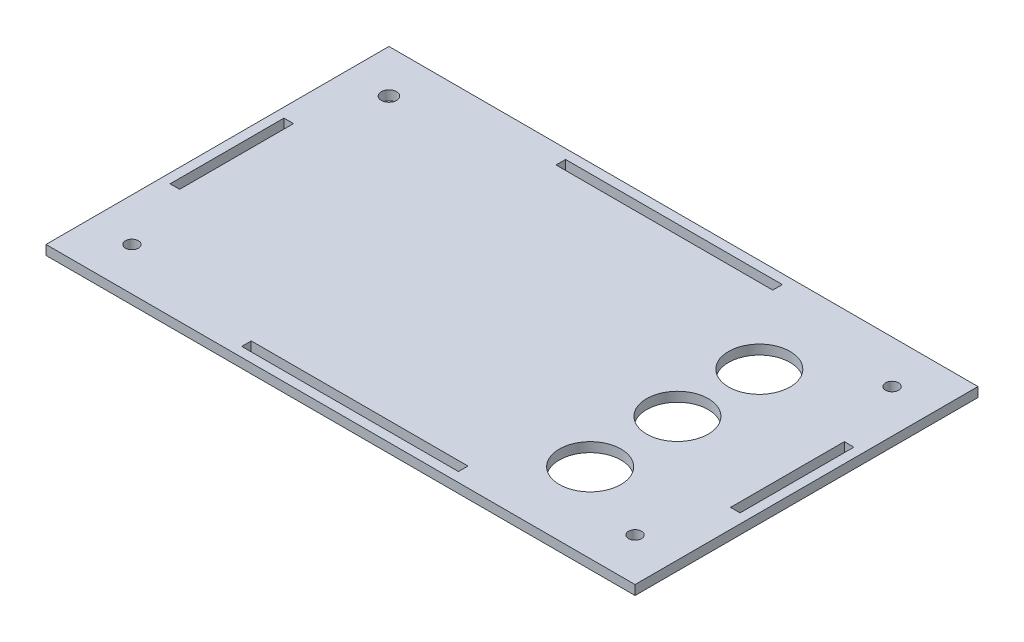
SolidWorks part; units mm, degrees
ref_plane "Front Plane" through (0, 0, 0) normal (0, 0, 1) x (1, 0, 0)
ref_plane "Top Plane" through (0, 0, 0) normal (0, 1, 0) x (1, 0, 0)
ref_plane "Right Plane" through (0, 0, 0) normal (1, 0, 0) x (0, 0, -1)
sketch "Sketch2" plane through (0, 0, 0) normal (0, 1, 0) x (1, 0, 0)
  line L15 (-5.2235, 66.6261) -> (118.1865, 66.6261)
  line L16 (-5.2235, 66.6261) -> (-5.2235, -5.2219)
  line L17 (-5.2235, -5.2219) -> (118.1865, -5.2219)
  line L18 (118.1865, 66.6261) -> (118.1865, -5.2219)
  line L19 (-1.2235, 42.6261) -> (-3.2235, 42.6261)
  line L20 (-1.2235, 42.6261) -> (-1.2235, 18.7781)
  line L21 (-1.2235, 18.7781) -> (-3.2235, 18.7781)
  line L22 (-3.2235, 42.6261) -> (-3.2235, 18.7781)
  line L23 (33.7765, 62.6261) -> (79.1865, 62.6261)
  line L24 (33.7765, 62.6261) -> (33.7765, 64.6261)
  line L25 (33.7765, 64.6261) -> (79.1865, 64.6261)
  line L26 (79.1865, 62.6261) -> (79.1865, 64.6261)
  line L27 (114.1865, 42.6261) -> (116.1865, 42.6261)
  line L28 (114.1865, 42.6261) -> (114.1865, 18.7781)
  line L29 (114.1865, 18.7781) -> (116.1865, 18.7781)
  line L30 (116.1865, 42.6261) -> (116.1865, 18.7781)
  line L31 (79.1865, -1.2219) -> (33.7765, -1.2219)
  line L32 (79.1865, -1.2219) -> (79.1865, -3.2219)
  line L33 (79.1865, -3.2219) -> (33.7765, -3.2219)
  line L34 (33.7765, -1.2219) -> (33.7765, -3.2219)
  circle A0 centre (3.7765, 3.7781) radius 1.3609
  circle A1 centre (109.1865, 3.7781) radius 1.3609
  circle A2 centre (3.7765, 57.6261) radius 1.6
  circle A3 centre (109.1865, 57.6261) radius 1.3609
  circle A4 centre (92.1137, 29.7296) radius 6.45
  circle A5 centre (92.1137, 11.4423) radius 6.45
  circle A6 centre (92.1319, 46.8635) radius 6.45
  point P34 (33.7765, -2.2219)
  point P35 (115.1865, 42.6261)
  dimension "D1" = 105.41
  dimension "D2" = 53.848
  dimension "D3" = 15
  dimension "D4" = 15
  dimension "D5" = 30
  dimension "D6" = 30
  dimension "D7" = 30
  dimension "D8" = 30
  dimension "D9" = 15
  dimension "D10" = 15
  dimension "D11" = 5
  dimension "D12" = 2
  dimension "D13" = 5
  dimension "D14" = 5
  dimension "D15" = 5
  dimension "D16" = 9
  dimension "D17" = 9
  dimension "D18" = 9
  dimension "D19" = 9
extrude "Boss-Extrude1" add sketch "Sketch2" along normal blind 2
